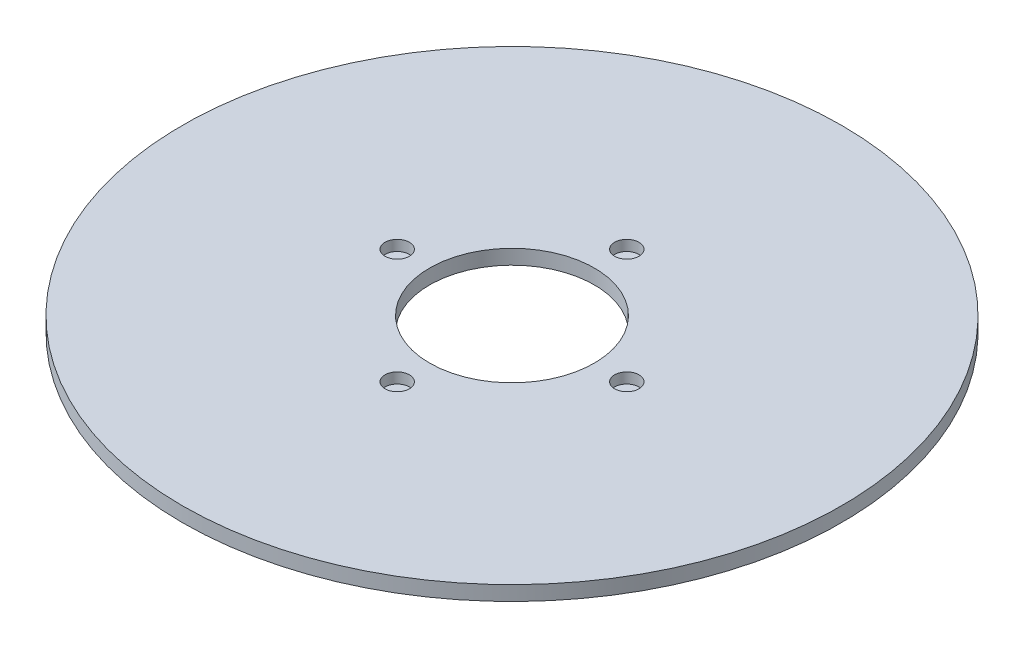
SolidWorks part; units mm, degrees
ref_plane "Front Plane" through (0, 0, 0) normal (0, 0, 1) x (1, 0, 0)
ref_plane "Top Plane" through (0, 0, 0) normal (0, 1, 0) x (1, 0, 0)
ref_plane "Right Plane" through (0, 0, 0) normal (1, 0, 0) x (0, 0, -1)
sketch "Sketch1" plane through (0, 0, 0) normal (0, 1, 0) x (1, 0, 0)
  circle A0 centre (0, 0) radius 90
  dimension "FLANGE_OD" = 180
extrude "Boss-Extrude1" add sketch "Sketch1" along normal blind 4
sketch "Sketch2" plane through (0, 0, 0) normal (0, 1, 0) x (1, 0, 0)
  circle A0 centre (0, 0) radius 22.5
  dimension "BORE_D" = 45
extrude "Cut-Extrude1" cut sketch "Sketch2" along normal through all
sketch "Sketch3" plane through (0, 4, 0) normal (0, 1, 0) x (1, 0, 0)
  circle A0 centre (0, 0) radius 31.3493 construction
  circle A1 centre (-31.3493, 0) radius 3.3224
  dimension "BOLT_D" = 6.6448
  dimension "BOLT_PCD" = 62.6987
extrude "Cut-Extrude2" cut sketch "Sketch3" against normal blind 2.8782
pattern_circular "CirPattern1" count 4 over 360 about axis through (0, 0, 0) along (0, 1, 0) of "Cut-Extrude2"
